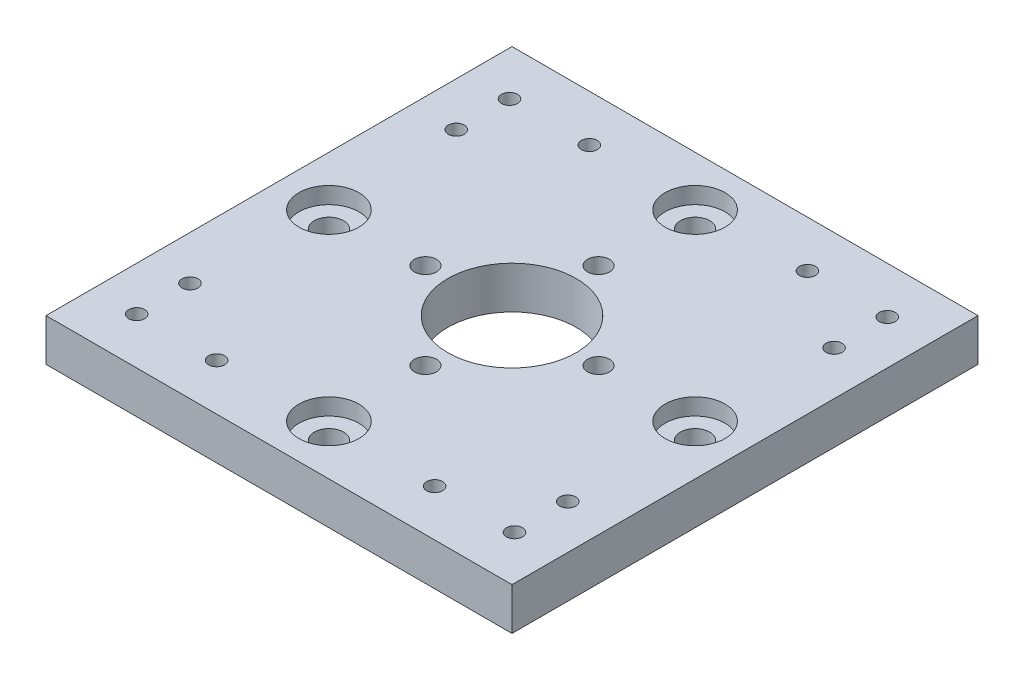
SolidWorks part; units mm, degrees
ref_plane "Front Plane" through (0, 0, 0) normal (0, 0, 1) x (1, 0, 0)
ref_plane "Top Plane" through (0, 0, 0) normal (0, 1, 0) x (1, 0, 0)
ref_plane "Right Plane" through (0, 0, 0) normal (1, 0, 0) x (0, 0, -1)
sketch "Sketch1" plane through (0, 0, 0) normal (0, 1, 0) x (1, 0, 0)
  line L1 (-35, -35) -> (35, -35)
  line L2 (-35, -35) -> (-35, 35)
  line L3 (-35, 35) -> (35, 35)
  line L4 (35, -35) -> (35, 35)
  line L5 (-35, -35) -> (35, 35) construction
  line L6 (-35, 35) -> (35, -35) construction
  circle A1 centre (0, 0) radius 13
  circle A2 centre (0, 13) radius 1.65
  circle A3 centre (13, 0) radius 1.65
  circle A4 centre (0, -13) radius 1.65
  circle A5 centre (-13, 0) radius 1.65
  point P1 (0, 0)
  dimension "D1" = 26
  dimension "D2" = 3.3
  dimension "D3" = 70
  dimension "D4" = 70
extrude "Boss-Extrude1" add sketch "Sketch1" along normal blind 6.35 contours A5 A1 A2 A3 A4 | A5 A1 A4 A3 A2 region at (-34.0101, 0, 0) region at (0, 0, 0)
sketch "Sketch2" plane through (0, 6.35, 0) normal (0, 1, 0) x (1, 0, 0)
  line L0 (0, 0) -> (0, 50000) construction
  line L1 (0, 0) -> (-50000, 0) construction
  circle A0 centre (16.375, 28) radius 1.2
  circle A1 centre (28.375, 28) radius 1.2
  circle A2 centre (28.375, 20) radius 1.2
  circle A3 centre (-28.375, 20) radius 1.2
  circle A4 centre (-28.375, 28) radius 1.2
  circle A5 centre (-16.375, 28) radius 1.2
  circle A6 centre (28.375, -20) radius 1.2
  circle A7 centre (28.375, -28) radius 1.2
  circle A8 centre (16.375, -28) radius 1.2
  circle A9 centre (-16.375, -28) radius 1.2
  circle A10 centre (-28.375, -20) radius 1.2
  circle A11 centre (-28.375, -28) radius 1.2
  dimension "D1" = 2.4
  dimension "D2" = 8
  dimension "D3" = 12
  dimension "D5" = 16.375
  dimension "D4" = 20
extrude "Cut-Extrude1" cut sketch "Sketch2" against normal up to next
sketch "Sketch3" plane through (0, 6.35, 0) normal (0, 1, 0) x (1, 0, 0)
  circle A0 centre (0, 0) radius 9.65
  dimension "D1" = 19.3
extrude "Cut-Extrude2" cut sketch "Sketch3" against normal up to next
sketch "Sketch4" plane through (0, 6.35, 0) normal (0, 1, 0) x (1, 0, 0)
  circle A0 centre (0, 0) radius 27.5
  circle A1 centre (0, 27.5) radius 2.2
  circle A2 centre (27.5, 0) radius 2.2
  circle A3 centre (0, -27.5) radius 2.2
  circle A4 centre (-27.5, 0) radius 2.2
  point P13 (0, 0)
  dimension "D1" = 55
  dimension "D2" = 4.4
  dimension "D3" = 4
extrude "Cut-Extrude3" cut sketch "Sketch4" against normal up to next contours A0 A4 | A0 A4 | A0 A1 | A0 A1 | A0 A2 | A0 A2 | A0 A3 | A0 A3 region at (26.5506, 6.35, 0) region at (28.4177, 6.35, 0) region at (0, 6.35, -26.5506) region at (0, 6.35, -28.4177) region at (0, 6.35, 28.4177) region at (0, 6.35, 26.5506) region at (-26.5506, 6.35, 0) region at (-28.4177, 6.35, 0)
sketch "Sketch5" plane through (0, 6.35, 0) normal (0, 1, 0) x (1, 0, 0)
  circle A0 centre (0, 27.5) radius 4.5
  circle A1 centre (27.5, 0) radius 4.5
  circle A2 centre (0, -27.5) radius 4.5
  circle A3 centre (-27.5, 0) radius 4.5
  dimension "D1" = 9
extrude "Cut-Extrude4" cut sketch "Sketch5" against normal blind 2.5
